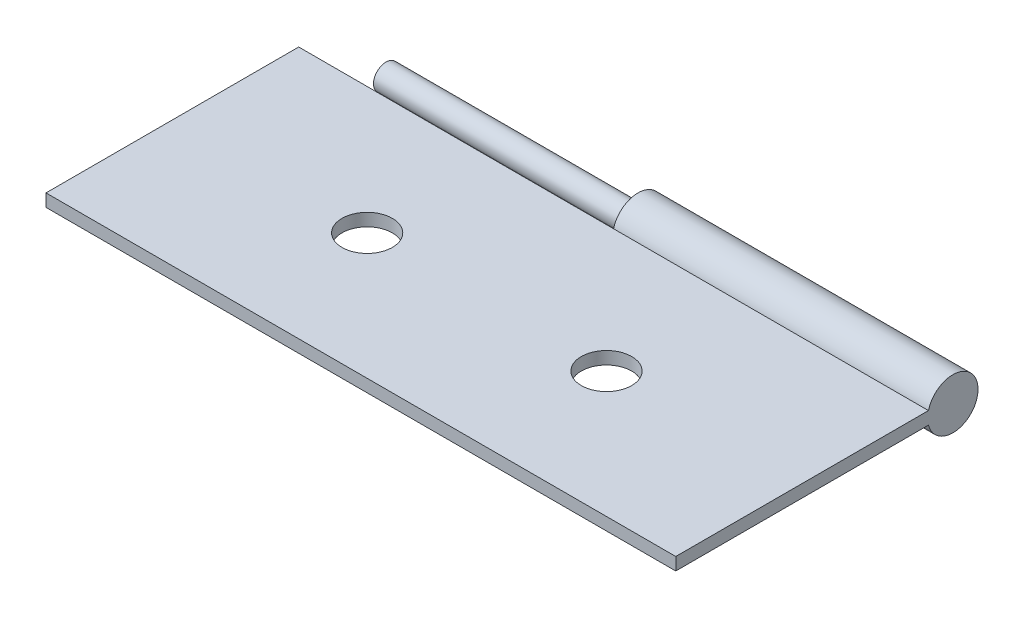
SolidWorks part; units mm, degrees
ref_plane "Front Plane" through (0, 0, 0) normal (0, 0, 1) x (1, 0, 0)
ref_plane "Top Plane" through (0, 0, 0) normal (0, 1, 0) x (1, 0, 0)
ref_plane "Right Plane" through (0, 0, 0) normal (1, 0, 0) x (0, 0, -1)
sketch "Sketch1" plane through (0, 0, 0) normal (0, 1, 0) x (1, 0, 0)
  line L1 (25, 10) -> (-25, 10)
  line L2 (25, 10) -> (25, -10)
  line L3 (25, -10) -> (-25, -10)
  line L4 (-25, 10) -> (-25, -10)
  line L5 (25, 10) -> (-25, -10) construction
  line L6 (25, -10) -> (-25, 10) construction
  point P0 (0, 0)
  dimension "D1" = 50
  dimension "D2" = 20
extrude "Boss-Extrude1" add sketch "Sketch1" along normal mid plane 1
sketch "Sketch2" plane through (25, 0, 0) normal (1, 0, 0) x (0, 0, -1)
  circle A0 centre (12, 0) radius 2
  dimension "D1" = 4
  dimension "D2" = 12
extrude "Boss-Extrude2" add sketch "Sketch2" against normal blind 25
sketch "Sketch3" plane through (0, 0, 0) normal (-1, 0, 0) x (0, 0, 1)
  circle A0 centre (-12, 0) radius 1
  dimension "D1" = 2
extrude "Boss-Extrude3" add sketch "Sketch3" along normal blind 20
sketch "Sketch4" plane through (0, 0, -10) normal (0, 0, -1) x (-1, 0, 0)
  line L4 (-25, 0.5) -> (-25, -0.5)
  line L5 (-25, -0.5) -> (25, -0.5)
  line L6 (25, -0.5) -> (25, 0.5)
  line L7 (25, 0.5) -> (-25, 0.5)
  line L8 (-25, 0.5) -> (-25, -0.5)
  line L9 (-25, -0.5) -> (25, -0.5)
  line L10 (25, -0.5) -> (25, 0.5)
  line L11 (25, 0.5) -> (-25, 0.5)
  dimension "D1" = 0
extrude "Boss-Extrude4" add sketch "Sketch4" along direction (0, 0, 1) on the side of the normal up to surface up to face at (0, 0, -14)
sketch "Sketch5" plane through (0, 0.5, 0) normal (0, 1, 0) x (1, 0, 0)
  line L0 (0, 0) -> (0, -10) construction
  line L1 (-25, -10) -> (25, -10) construction
  circle A0 centre (9.5, 0) radius 2
  circle A1 centre (-9.5, 0) radius 2
  dimension "D1" = 4
  dimension "D2" = 9.5
extrude "Cut-Extrude1" cut sketch "Sketch5" against normal through all
